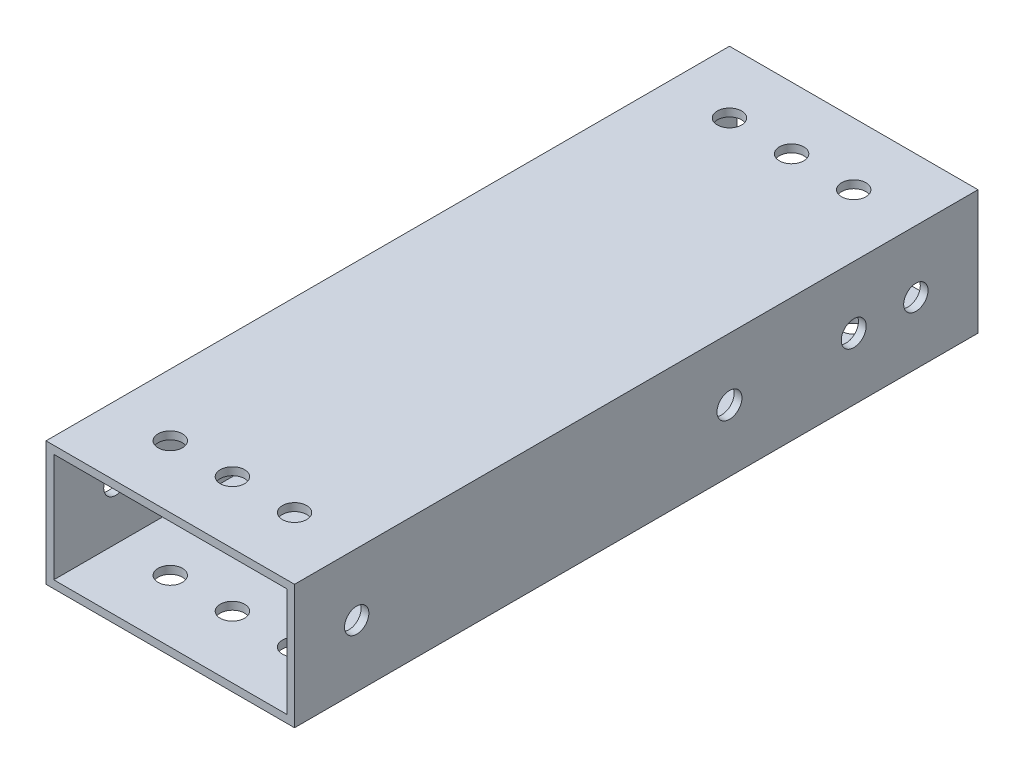
SolidWorks part; units mm, degrees
material "6061-T6 (SS)"
ref_plane "Front Plane" through (0, 0, 0) normal (0, 0, 1) x (1, 0, 0)
ref_plane "Top Plane" through (0, 0, 0) normal (0, 1, 0) x (1, 0, 0)
ref_plane "Right Plane" through (0, 0, 0) normal (1, 0, 0) x (0, 0, -1)
sketch "Sketch1" plane through (0, 0, 0) normal (0, 0, 1) x (1, 0, 0)
  line L0 (-23.8125, 11.1125) -> (23.8125, 11.1125)
  line L1 (-25.4, -12.7) -> (25.4, -12.7)
  line L2 (-25.4, -12.7) -> (-25.4, 12.7)
  line L3 (-25.4, 12.7) -> (25.4, 12.7)
  line L4 (25.4, -12.7) -> (25.4, 12.7)
  line L5 (-25.4, -12.7) -> (25.4, 12.7) construction
  line L6 (-25.4, 12.7) -> (25.4, -12.7) construction
  line L7 (23.8125, -11.1125) -> (23.8125, 11.1125)
  line L8 (-23.8125, -11.1125) -> (23.8125, -11.1125)
  line L9 (-23.8125, -11.1125) -> (-23.8125, 11.1125)
  point P0 (0, 0)
  dimension "D1" = 50.8
  dimension "D2" = 25.4
  dimension "D3" = 1.5875
extrude "Boss-Extrude1" add sketch "Sketch1" along normal mid plane 139.7
sketch "Sketch2" plane through (0, 12.7, 0) normal (0, 1, 0) x (1, 0, 0)
  line L0 (25.4, 69.85) -> (-25.4, 69.85) construction
  line L1 (25.4, 0) -> (-25.4, 0) construction
  line L2 (25.4, -69.85) -> (25.4, 69.85) construction
  line L3 (-25.4, -69.85) -> (-25.4, 69.85) construction
  circle A0 centre (-12.7, 57.15) radius 2.4892
  circle A1 centre (0, 57.15) radius 2.4892
  circle A2 centre (12.7, 57.15) radius 2.4892
  circle A3 centre (12.7, -57.15) radius 2.4892
  circle A4 centre (0, -57.15) radius 2.4892
  circle A5 centre (-12.7, -57.15) radius 2.4892
  dimension "D4" = 4.9784
  dimension "D1" = 12.7
  dimension "D2" = 12.7
  dimension "D3" = 12.7
extrude "Cut-Extrude1" cut sketch "Sketch2" against normal through all
sketch "Sketch3" plane through (-25.4, 0, 0) normal (-1, 0, 0) x (0, 0, 1)
  line L0 (-69.85, 12.7) -> (-69.85, -12.7) construction
  line L1 (0, 12.7) -> (0, -12.7) construction
  line L2 (69.85, 12.7) -> (-69.85, 12.7) construction
  line L3 (69.85, -12.7) -> (-69.85, -12.7) construction
  circle A0 centre (-57.15, 0) radius 2.4892
  circle A1 centre (57.15, 0) radius 2.4892
  dimension "D1" = 4.9784
  dimension "D2" = 12.7
extrude "Cut-Extrude2" cut sketch "Sketch3" against normal through all contours A1 | A0
sketch "Sketch5" plane through (25.4, 0, 0) normal (1, 0, 0) x (0, 0, -1)
  line L0 (69.85, -12.7) -> (69.85, 12.7) construction
  circle A1 centre (44.45, 0) radius 2.5527
  circle A2 centre (19.05, 0) radius 2.5527
  dimension "D1" = 25.4
  dimension "D3" = 5.1054
  dimension "D4" = 25.4
extrude "Cut-Extrude3" cut sketch "Sketch5" against normal through all
